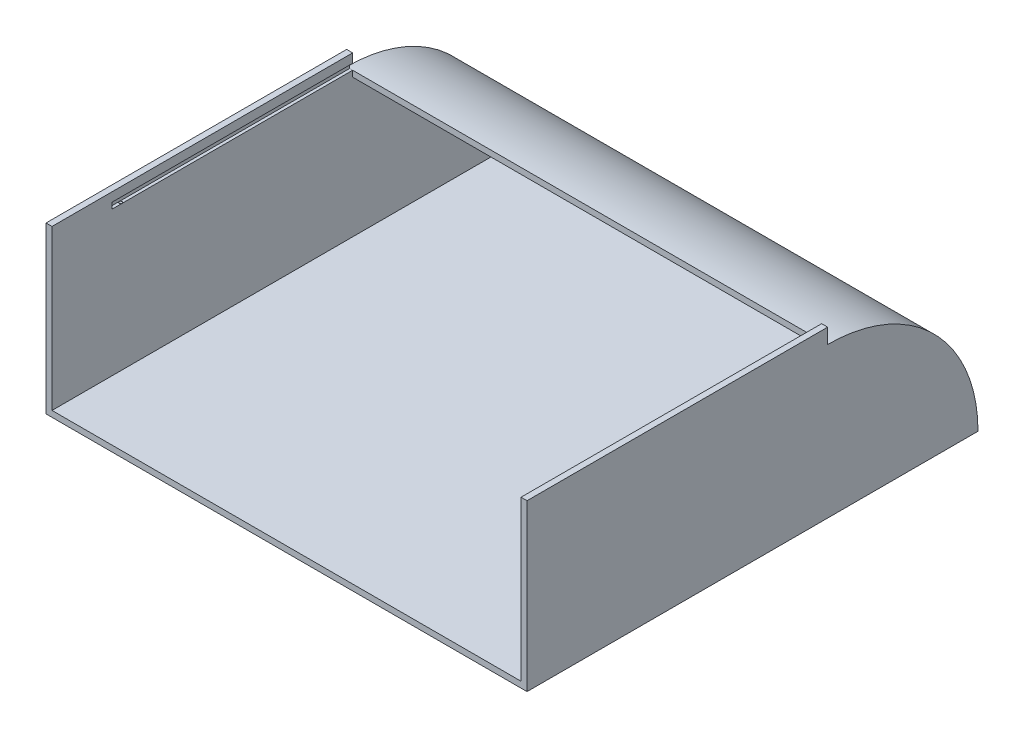
SolidWorks part; units mm, degrees
ref_plane "Front Plane" through (0, 0, 0) normal (0, 0, 1) x (1, 0, 0)
ref_plane "Top Plane" through (0, 0, 0) normal (0, 1, 0) x (1, 0, 0)
ref_plane "Right Plane" through (0, 0, 0) normal (1, 0, 0) x (0, 0, -1)
sketch "Sketch1" plane through (0, 0, 0) normal (1, 0, 0) x (0, 0, -1)
  line L1 (75, -25) -> (-75, -25)
  line L2 (75, -25) -> (75, 25)
  line L3 (75, 25) -> (-75, 25)
  line L4 (-75, -25) -> (-75, 25)
  line L5 (75, -25) -> (-75, 25) construction
  line L6 (75, 25) -> (-75, -25) construction
  point P0 (0, 0)
  dimension "D1" = 50
  dimension "D2" = 150
extrude "Boss-Extrude1" add sketch "Sketch1" against normal blind 160
fillet "Fillet2" radius 50 1 edges at (-80, 25, -75)
sketch "Sketch17" plane through (0, 25, 0) normal (0, 1, 0) x (1, 0, 0)
  line L0 (-80, 25) -> (-158, 25)
  line L1 (0, 25) -> (-160, 25) construction
  line L2 (-80, 25) -> (-2, 25)
  line L7 (-158, 25) -> (-158, -75)
  line L8 (-160, -75) -> (0, -75) construction
  line L9 (-2, 25) -> (-2, -75)
  line L10 (-2, -75) -> (-158, -75)
shell "Shell1" thickness 2 removed face at (-80, 0, 75)
extrude "Cut-Extrude1" cut sketch "Sketch17" against normal blind 2
sketch "Sketch20" plane through (0, 25, 0) normal (0, 1, 0) x (1, 0, 0)
  line L1 (-160, 25) -> (-158, 25)
  line L2 (-160, 25) -> (-160, -75)
  line L3 (-160, -75) -> (-158, -75)
  line L4 (-158, 25) -> (-158, -75)
  line L5 (-2, 25) -> (0, 25)
  line L6 (-2, 25) -> (-2, -75)
  line L7 (-2, -75) -> (0, -75)
  line L8 (0, 25) -> (0, -75)
extrude "Boss-Extrude2" add sketch "Sketch20" along normal blind 5
sketch "Sketch21" plane through (-158, 0, 0) normal (1, 0, 0) x (0, 0, -1)
  line L1 (25, 25) -> (-55, 25)
  line L2 (25, 25) -> (25, 27)
  line L3 (25, 27) -> (-55, 27)
  line L4 (-55, 25) -> (-55, 27)
  dimension "D1" = 80
  dimension "D2" = 2
extrude "Cut-Extrude2" cut sketch "Sketch21" against normal blind 1
sketch "Sketch22" plane through (-2, 0, 0) normal (-1, 0, 0) x (0, 0, 1)
  line L1 (-25, 25) -> (55, 25)
  line L2 (-25, 25) -> (-25, 27)
  line L3 (-25, 27) -> (55, 27)
  line L4 (55, 25) -> (55, 27)
  dimension "D1" = 80
  dimension "D2" = 2
extrude "Cut-Extrude3" cut sketch "Sketch22" against normal blind 1
sketch "Sketch24" plane through (0, 25, 0) normal (0, 1, 0) x (1, 0, 0)
  line L0 (-2, 25) -> (-2, -55) construction
  line L1 (-1, -55) -> (-2, -55) construction
  circle A0 centre (-1.5, -50) radius 0.5
  dimension "D1" = 0.5
  dimension "D2" = 5
sketch "Sketch25" plane through (0, 25, 0) normal (0, 1, 0) x (1, 0, 0)
  line L0 (-1.5, -50) -> (-1.4753, -50.4994)
  line L1 (-1.5, -50) -> (-1.5247, -49.5006)
  line L2 (-2, -55) -> (-2, 25) construction
  arc A0 (-1.4753, -50.4994) -> (-1.5247, -49.5006) centre (-1.5, -50) cw
  dimension "D1" = 0.5
  dimension "D2" = 0.5
revolve "Cut-Revolve1" cut sketch "Sketch25" angle 360 about L1 region at (-1.7119, 25, 50.0105)
sketch "Sketch26" plane through (0, 25, 0) normal (0, 1, 0) x (1, 0, 0)
  line L0 (-158, -51.6764) -> (-159, -51.6764)
  line L1 (-158, -55) -> (-158, 25) construction
  line L2 (-159, -55) -> (-159, 25) construction
  arc A0 (-158, -51.6764) -> (-159, -51.6764) centre (-158.5, -51.6764) cw
revolve "Cut-Revolve2" cut sketch "Sketch26" angle 360 about L0
